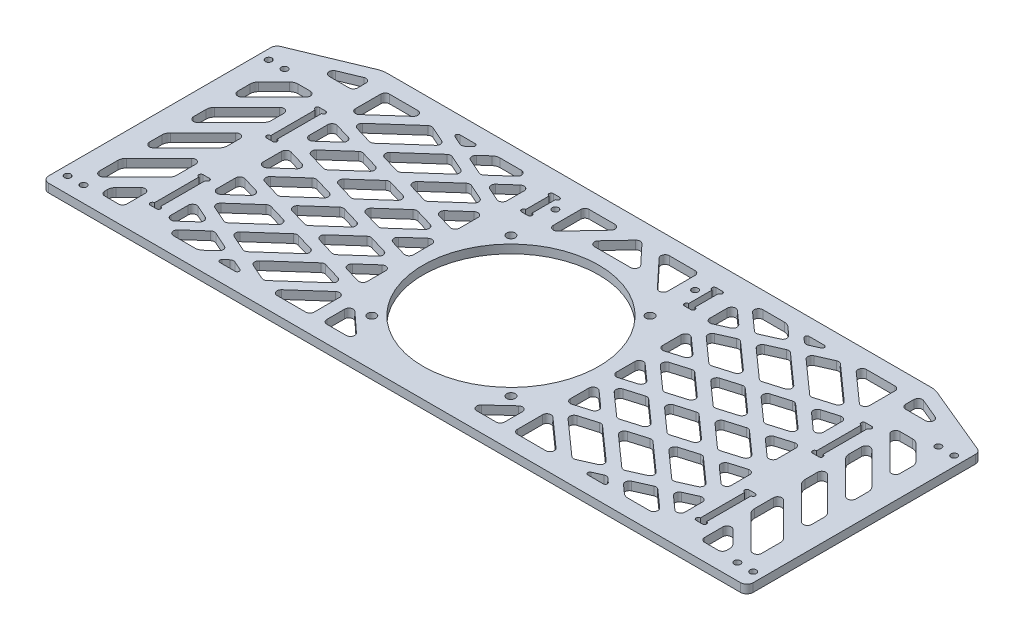
SolidWorks part; units mm, degrees
material "Thornel Mat VMA"
ref_plane "前视基准面" through (0, 0, 0) normal (0, 0, 1) x (1, 0, 0)
ref_plane "上视基准面" through (0, 0, 0) normal (0, 1, 0) x (1, 0, 0)
ref_plane "右视基准面" through (0, 0, 0) normal (1, 0, 0) x (0, 0, -1)
sketch "草图1" plane through (0, 0, 0) normal (0, 1, 0) x (1, 0, 0)
  line L6 (0, -55) -> (0, 55) construction
  line L7 (-33, 54) -> (33, 54) construction
  line L19 (-166.5, -55) -> (166.5, -55)
  line L20 (-166.5, 55) -> (-166.5, -55)
  line L21 (166.5, 55) -> (166.5, -55)
  line L24 (-130.5, 40) -> (-127.5, 40)
  line L25 (-130.5, 40) -> (-130.5, 15)
  line L26 (-130.5, 15) -> (-127.5, 15)
  line L27 (-127.5, 40) -> (-127.5, 15)
  line L30 (130.5, -40) -> (127.5, -40)
  line L31 (130.5, -15) -> (130.5, -40)
  line L32 (127.5, -15) -> (130.5, -15)
  line L33 (127.5, -40) -> (127.5, -15)
  line L34 (127.5, 40) -> (127.5, 15)
  line L35 (-127.5, -40) -> (-127.5, -15)
  line L36 (-127.5, -15) -> (-130.5, -15)
  line L37 (-130.5, -15) -> (-130.5, -40)
  line L38 (-130.5, -40) -> (-127.5, -40)
  line L39 (130.5, 15) -> (127.5, 15)
  line L40 (130.5, 40) -> (130.5, 15)
  line L41 (130.5, 40) -> (127.5, 40)
  line L47 (-154.5, -47.5) -> (-162, -47.5) construction
  line L48 (-154.5, -47.5) -> (-154.5, 47.5) construction
  line L49 (-154.5, 47.5) -> (-162, 47.5) construction
  line L50 (-162, -47.5) -> (-162, 47.5) construction
  line L51 (-166.5, 55) -> (-130.5, 70)
  line L52 (-130.5, 70) -> (130.5, 70)
  line L56 (166.5, 55) -> (130.5, 70)
  line L57 (-166.5, 0) -> (0, 0) construction
  line L58 (-130.5, 15) -> (-130.5, -15) construction
  circle A0 centre (0, 0) radius 41.5
  circle A3 centre (-33, 54) radius 1.5
  circle A5 centre (33, 54) radius 1.5
  circle A8 centre (-162, 47.5) radius 1.5
  circle A9 centre (-154.5, 47.5) radius 1.5
  circle A10 centre (-154.5, -47.5) radius 1.5
  circle A11 centre (-162, -47.5) radius 1.5
  circle A12 centre (154.5, -47.5) radius 1.5
  circle A13 centre (162, -47.5) radius 1.5
  circle A14 centre (154.5, 47.5) radius 1.5
  circle A15 centre (162, 47.5) radius 1.5
  point P11 (0, 54)
  point P13 (-130.5, 0)
  point P16 (-154.5, 0)
  dimension "D1" = 83
  dimension "D5" = 261
  dimension "D8" = 3
  dimension "D26" = 3
  dimension "D3" = 66
  dimension "D4" = 15
  dimension "D6" = 16
  dimension "D12" = 333
  dimension "D17" = 3
  dimension "D18" = 25
  dimension "D19" = 30
  dimension "D20" = 127.5
  dimension "D22" = 4.5
  dimension "D23" = 7.5
  dimension "D24" = 95
  dimension "D25" = 7.5
extrude "凸台-拉伸1" add sketch "草图1" along normal blind 4
sketch "草图2" plane through (0, 4, 0) normal (0, 1, 0) x (1, 0, 0)
  line L1 (40, 45) -> (40, 60)
  line L2 (0, 21.0132) -> (0, 0) construction
  line L3 (0, 0) -> (21.2014, 0) construction
  line L4 (-32.8805, 32.8805) -> (0, 0) construction
  line L5 (-37, 45) -> (-40, 45)
  line L6 (-37, 45) -> (-37, 60)
  line L7 (-37, 60) -> (-40, 60)
  line L8 (-40, 45) -> (-40, 60)
  line L9 (37, 60) -> (40, 60)
  line L10 (37, 45) -> (37, 60)
  line L11 (37, 45) -> (40, 45)
  line L12 (130.5, 70) -> (-130.5, 70) construction
  circle A7 centre (-32.8805, 32.8805) radius 2
  circle A9 centre (32.8805, 32.8805) radius 2
  circle A18 centre (0, 0) radius 46.5 construction
  circle A21 centre (32.8805, -32.8805) radius 2
  circle A23 centre (-32.8805, -32.8805) radius 2
  dimension "D1" = 93
  dimension "D2" = 4
  dimension "D3" = 74
  dimension "D4" = 3
  dimension "D5" = 10
  dimension "D6" = 15
  dimension "D7" = 45
extrude "切除-拉伸1" cut sketch "草图2" against normal through all
sketch "草图3" plane through (0, 4, 0) normal (0, 1, 0) x (1, 0, 0)
  line L0 (-40, 60) -> (-40, 45) construction
  line L1 (-37, 45) -> (-37, 60) construction
  line L2 (0, -55) -> (0, 55) construction
  line L5 (-130.5, 40) -> (-130.5, 15) construction
  line L6 (-127.5, 15) -> (-127.5, 40) construction
  line L7 (-130.5, -15) -> (-130.5, -40) construction
  line L8 (-127.5, -40) -> (-127.5, -15) construction
  circle A0 centre (-40, 59) radius 1
  circle A1 centre (-37, 59) radius 1
  circle A2 centre (-37, 46) radius 1
  circle A3 centre (-40, 46) radius 1
  circle A4 centre (40, 46) radius 1
  circle A5 centre (37, 46) radius 1
  circle A6 centre (37, 59) radius 1
  circle A7 centre (40, 59) radius 1
  circle A12 centre (-130.5, 39) radius 1
  circle A13 centre (-127.5, 39) radius 1
  circle A14 centre (-127.5, 16) radius 1
  circle A15 centre (-130.5, 16) radius 1
  circle A16 centre (-130.5, -16) radius 1
  circle A17 centre (-127.5, -16) radius 1
  circle A18 centre (-127.5, -39) radius 1
  circle A19 centre (-130.5, -39) radius 1
  circle A20 centre (130.5, -39) radius 1
  circle A21 centre (127.5, -39) radius 1
  circle A22 centre (127.5, -16) radius 1
  circle A23 centre (130.5, -16) radius 1
  circle A24 centre (130.5, 16) radius 1
  circle A25 centre (127.5, 16) radius 1
  circle A26 centre (127.5, 39) radius 1
  circle A27 centre (130.5, 39) radius 1
  dimension "D1" = 2
extrude "切除-拉伸2" cut sketch "草图3" against normal through all
sketch "草图12" plane through (0, 4, 0) normal (0, 1, 0) x (1, 0, 0)
  line L0 (-136.5, -7.6406) -> (-136.5, -23.0777)
  line L3 (-136.5, 13.2041) -> (-136.5, 0.8447)
  line L4 (-156.5, 14.0487) -> (-156.5, 1.6893)
  line L5 (-156.5, -6.7959) -> (-156.5, -19.1553)
  line L6 (-156.5, -27.6406) -> (-156.5, -40)
  line L9 (-136.5, -31.5629) -> (-147, -42.0629)
  line L10 (-147, -47) -> (-136.5, -47)
  line L32 (-136.5, -47) -> (-136.5, -31.5629)
  line L41 (-146.8594, 44.534) -> (-156.5, 34.8934)
  line L44 (-166.5, -55) -> (166.5, -55) construction
  line L73 (-147, -42.0629) -> (-147, -47)
  line L74 (-129.5, 63.9167) -> (-150.9, 55)
  line L75 (-150.9, 55) -> (-129.5, 55)
  line L76 (-129.5, 55) -> (-129.5, 63.9167)
  line L77 (-42, -32) -> (-25.7448, -47)
  line L78 (-25.7448, -47) -> (-42, -47)
  line L79 (-42, -47) -> (-42, -32)
  line L84 (-130.5, 70) -> (-166.5, 55) construction
  line L85 (-166.5, -55) -> (166.5, -55) construction
  line L96 (-121.5, 62) -> (-48, 62)
  line L97 (-121.5, 62) -> (-121.5, -47)
  line L99 (-121.5, -47) -> (-48, -47)
  line L102 (-48, 62) -> (-48, -47)
  line L107 (-136.5, 21.6893) -> (-156.5, 1.6893)
  line L108 (-146.8594, 44.534) -> (-134.5, 44.534)
  line L109 (-156.5, 34.8934) -> (-156.5, 22.534)
  line L110 (-156.5, -40) -> (-153.4223, -40)
  line L111 (-136.5, 34.0487) -> (-136.5, 21.6893)
  line L112 (-136.5, 13.2041) -> (-156.5, -6.7959)
  line L113 (-136.5, 0.8447) -> (-156.5, -19.1553)
  line L114 (-156.5, -27.6406) -> (-136.5, -7.6406)
  line L115 (-136.5, -23.0777) -> (-153.4223, -40)
  line L117 (-130.5, 38) -> (-130.5, 17) construction
  line L118 (-136.5, 34.0487) -> (-156.5, 14.0487)
  line L119 (-127.5, -38) -> (-127.5, -17) construction
  line L120 (-134.5, 44.534) -> (-156.5, 22.534)
  line L121 (-166.5, 55) -> (-166.5, -55) construction
  line L126 (-40, 58) -> (-40, 47) construction
  line L187 (130.5, 70) -> (-130.5, 70) construction
  line L188 (0, -2.2) -> (0, 2.2) construction
  line L189 (134.5, 44.534) -> (156.5, 22.534)
  line L190 (136.5, 34.0487) -> (156.5, 14.0487)
  line L191 (136.5, -23.0777) -> (153.4223, -40)
  line L192 (156.5, -27.6406) -> (136.5, -7.6406)
  line L193 (136.5, 0.8447) -> (156.5, -19.1553)
  line L194 (136.5, 13.2041) -> (156.5, -6.7959)
  line L195 (136.5, 34.0487) -> (136.5, 21.6893)
  line L196 (156.5, -40) -> (153.4223, -40)
  line L197 (156.5, 34.8934) -> (156.5, 22.534)
  line L198 (146.8594, 44.534) -> (134.5, 44.534)
  line L199 (136.5, 21.6893) -> (156.5, 1.6893)
  line L200 (48, 62) -> (48, -47)
  line L201 (121.5, -47) -> (48, -47)
  line L202 (121.5, 62) -> (121.5, -47)
  line L203 (121.5, 62) -> (48, 62)
  line L204 (42, -47) -> (42, -32)
  line L205 (25.7448, -47) -> (42, -47)
  line L206 (42, -32) -> (25.7448, -47)
  line L207 (129.5, 55) -> (129.5, 63.9167)
  line L208 (150.9, 55) -> (129.5, 55)
  line L209 (129.5, 63.9167) -> (150.9, 55)
  line L210 (147, -42.0629) -> (147, -47)
  line L211 (146.8594, 44.534) -> (156.5, 34.8934)
  line L212 (136.5, -47) -> (136.5, -31.5629)
  line L213 (147, -47) -> (136.5, -47)
  line L214 (136.5, -31.5629) -> (147, -42.0629)
  line L215 (156.5, -27.6406) -> (156.5, -40)
  line L216 (156.5, -6.7959) -> (156.5, -19.1553)
  line L217 (156.5, 14.0487) -> (156.5, 1.6893)
  line L218 (136.5, 13.2041) -> (136.5, 0.8447)
  line L219 (136.5, -7.6406) -> (136.5, -23.0777)
  line L220 (-27, 62) -> (-27, 42)
  line L221 (-27, 42) -> (-8.2288, 62)
  line L222 (-8.2288, 62) -> (-27, 62)
  line L223 (0, 62) -> (-13.1399, 48)
  line L224 (-13.1399, 48) -> (13.1399, 48)
  line L226 (0, 62) -> (13.1399, 48)
  line L227 (8.2288, 62) -> (27, 62)
  line L228 (27, 42) -> (8.2288, 62)
  line L229 (27, 62) -> (27, 42)
  line L230 (0, 62) -> (0, 48) construction
  circle A0 centre (-154.5, 47.5) radius 1.5 construction
  circle A1 centre (-154.5, -47.5) radius 1.5 construction
  circle A2 centre (0, 0) radius 41.5 construction
  circle A3 centre (-33, 54) radius 1.5 construction
  dimension "D3" = 8
  dimension "D17" = 15
  dimension "D27" = 6
  dimension "D11" = 7.5
  dimension "D18" = 7.5
  dimension "D24" = 6
  dimension "D4" = 6
  dimension "D5" = 6
  dimension "D6" = 6
  dimension "D7" = 6
  dimension "D8" = 135
  dimension "D9" = 7.5
  dimension "D10" = 4
  dimension "D12" = 6
  dimension "D13" = 8
  dimension "D14" = 6
  dimension "D15" = 52
  dimension "D16" = 8
  dimension "D19" = 6
  dimension "D20" = 6
  dimension "D21" = 10
  dimension "D22" = 15
  dimension "D23" = 8
  dimension "D25" = 8
  dimension "D26" = 48
  dimension "D28" = 20
extrude "切除-拉伸8" cut sketch "草图12" against normal through all
sketch "草图13" plane through (0, 4, 0) normal (0, 1, 0) x (1, 0, 0)
  line L0 (-97, 62) -> (-121.5, 40.2) construction
  line L1 (-48, 62) -> (-121.5, 62) construction
  line L2 (-121.5, 62) -> (-121.5, -47) construction
  line L3 (-72.5, 62) -> (-121.5, 18.4)
  line L4 (-121.5, 62) -> (-97, 62) construction
  line L5 (-48, 62) -> (-121.5, -3.4)
  line L6 (-121.5, -47) -> (-48, 18.4)
  line L7 (-48, -47) -> (-48, 62) construction
  line L8 (-121.5, 40.2) -> (-48, 18.4)
  line L9 (-97, -47) -> (-48, -3.4)
  line L10 (-97, 62) -> (-72.5, 62) construction
  line L11 (-121.5, -47) -> (-48, -47) construction
  line L12 (-72.5, 62) -> (-48, 62) construction
  line L13 (-121.5, -25.2) -> (-48, 40.2)
  line L14 (-121.5, 62) -> (-121.5, 40.2) construction
  line L15 (-121.5, 40.2) -> (-121.5, 18.4) construction
  line L16 (-121.5, 18.4) -> (-121.5, -3.4) construction
  line L17 (-72.5, 62) -> (-70.2588, 63.9942)
  line L18 (-121.5, 18.4) -> (-48, -3.4)
  line L19 (-121.5, -3.4) -> (-48, -25.2)
  line L20 (-121.5, -3.4) -> (-121.5, -25.2) construction
  line L21 (-121.5, -25.2) -> (-121.5, -47) construction
  line L22 (-97, 62) -> (-48, 40.2)
  line L23 (-121.5, -25.2) -> (-72.5, -47)
  line L24 (0, -2.2) -> (0, 2.2) construction
  line L25 (-97, -47) -> (-99.2412, -48.9942)
  line L26 (-72.5, -47) -> (-48, -25.2) construction
  line L27 (72.5, -47) -> (48, -25.2) construction
  line L28 (97, -47) -> (99.2412, -48.9942)
  line L29 (72.5, 62) -> (70.2588, 63.9942)
  line L33 (121.5, -25.2) -> (72.5, -47)
  line L34 (97, 62) -> (48, 40.2)
  line L35 (121.5, -3.4) -> (48, -25.2)
  line L36 (121.5, 18.4) -> (48, -3.4)
  line L38 (121.5, -25.2) -> (48, 40.2)
  line L39 (97, -47) -> (48, -3.4)
  line L40 (121.5, 40.2) -> (48, 18.4)
  line L41 (121.5, -47) -> (48, 18.4)
  line L42 (48, 62) -> (121.5, -3.4)
  line L43 (72.5, 62) -> (121.5, 18.4)
  line L44 (97, 62) -> (121.5, 40.2) construction
  dimension "D1" = 3
extrude "拉伸-薄壁1" add sketch "草图13" against normal up to surface (4 mm away) thin contours L43 L36 L39 | L3 L18 L9 | L41 L40 L44 L34 L38 L33 L35 L42 | L6 L8 L0 L22 L13 L23 L19 L5 up to face at (-146.5, 0, -17.869) thin type mid plane wall 5
sketch "草图14" plane through (0, 4, 0) normal (0, 1, 0) x (1, 0, 0)
  line L0 (97, 62) -> (121.5, 40.2) construction
  line L1 (72.5, -47) -> (48, -25.2) construction
  line L2 (-72.5, -47) -> (-48, -25.2) construction
  line L3 (-97, 62) -> (-121.5, 40.2) construction
  line L4 (97, 62) -> (121.5, 40.2)
  line L5 (72.5, -47) -> (48, -25.2)
  line L6 (-72.5, -47) -> (-48, -25.2)
  line L7 (-97, 62) -> (-121.5, 40.2)
extrude "拉伸-薄壁2" add sketch "草图14" against normal up to surface (4 mm away) thin up to face at (104.15, 0, 42.4621) thin type mid plane wall 5
fillet "圆角1" radius 3 4 edges at (-166.5, 2, -55) (166.5, 2, 55) (-166.5, 2, 55) (166.5, 2, -55)
fillet "圆角2" radius 10 2 edges at (-130.5, 2, -70) (130.5, 2, -70)
fillet "圆角3" radius 4 22 edges at (-156.5, 2, -34.8934) (-136.5, 2, -0.8447) (-156.5, 2, 6.7959) (-156.5, 2, -14.0487) (-136.5, 2, -21.6893) (-156.5, 2, 27.6406) (-136.5, 2, 23.0777) (-146.8594, 2, -44.534) (147, 2, 42.0629) (156.5, 2, 27.6406) (156.5, 2, 6.7959) (136.5, 2, 23.0777) (136.5, 2, -0.8447) (136.5, 2, -21.6893) (156.5, 2, -14.0487) (156.5, 2, -34.8934) (146.8594, 2, -44.534) (-68.7391, 2, -62) (68.7391, 2, -62) (100.7609, 2, 47) (-100.7609, 2, 47) (-147, 2, 42.0629)
fillet "圆角4" radius 1 8 edges at (76.2609, 2, -62) (90.8497, 2, -62) (-76.2609, 2, -62) (-90.8497, 2, -62) (93.2391, 2, 47) (78.6503, 2, 47) (-78.6503, 2, 47) (-93.2391, 2, 47)
fillet "圆角5" radius 2 217 edges at (156.5, 2, 40) (-156.5, 2, 40) (-81.1238, 2, -57.673) (-109.724, 2, 33.1754) (-121.5, 2, 43.6536) (-121.5, 2, 27.9363) (-48, 2, -21.0076) (-61.3564, 2, -24.9691) (-48, 2, -36.8536) (-117.7391, 2, 47) (-104.7095, 2, 35.4063) (-93.3907, 2, 40.442) (-88.3762, 2, 42.673) (-121.5, 2, 6.0076) (-108.1436, 2, 9.9691) (-121.5, 2, 21.8536) (-121.5, 2, -37.5924) (-108.1436, 2, -33.6309) (-121.5, 2, -21.7464) (-121.5, 2, -15.7924) (-108.1436, 2, -11.8309) (-121.5, 2, 0.0536) (-64.7905, 2, -50.4063) (-76.1093, 2, -55.442) (-51.7609, 2, -62) (-59.776, 2, -48.1754) (-48, 2, -58.6536) (-48, 2, -42.9363) (-48, 2, 0.7924) (-61.3564, 2, -3.1691) (-48, 2, -15.0536) (-61.3564, 2, 18.6309) (-48, 2, 6.7464) (-48, 2, 22.5924) (-100.6093, 2, 31.758) (-84.1273, 2, 17.0923) (-71.3936, 2, 20.8691) (-89.2905, 2, 36.7937) (-116.9427, 2, 24.4913) (-102.5023, 2, 11.6423) (-89.7686, 2, 15.4191) (-105.6238, 2, 29.527) (-84.1273, 2, -4.7077) (-71.3936, 2, -0.9309) (-85.3727, 2, 11.5077) (-98.1064, 2, 7.7309) (-65.7523, 2, -21.0577) (-53.0186, 2, -17.2809) (-66.9977, 2, -4.8423) (-79.7314, 2, -8.6191) (-85.3727, 2, -32.0923) (-98.1064, 2, -35.8691) (-80.2095, 2, -51.7937) (-68.8907, 2, -46.758) (-116.4814, 2, 2.2809) (-102.5023, 2, -10.1577) (-89.7686, 2, -6.3809) (-103.7477, 2, 6.0577) (-98.1064, 2, -14.0691) (-84.1273, 2, -26.5077) (-71.3936, 2, -22.7309) (-85.3727, 2, -10.2923) (-52.5573, 2, -39.4913) (-66.9977, 2, -26.6423) (-79.7314, 2, -30.4191) (-63.8762, 2, -44.527) (-89.7686, 2, -28.1809) (-103.7477, 2, -15.7423) (-116.4814, 2, -19.5191) (-102.5023, 2, -31.9577) (-53.0186, 2, 4.5191) (-66.9977, 2, 16.9577) (-79.7314, 2, 13.1809) (-65.7523, 2, 0.7423) (-156.5, 2, -1.6893) (-136.5, 2, -34.0487) (0, 2, -62) (13.1399, 2, -48) (-13.1399, 2, -48) (-156.5, 2, 19.1553) (-136.5, 2, -13.2041) (-136.5, 2, 7.6406) (-153.4223, 2, 40) (147, 2, 47) (136.5, 2, 47) (136.5, 2, 31.5629) (129.5, 2, -63.9167) (150.9, 2, -55) (129.5, 2, -55) (42, 2, 32) (42, 2, 47) (25.7448, 2, 47) (156.5, 2, -1.6893) (136.5, 2, -34.0487) (156.5, 2, -22.534) (134.5, 2, -44.534) (156.5, 2, 19.1553) (136.5, 2, -13.2041) (153.4223, 2, 40) (136.5, 2, 7.6406) (-150.9, 2, -55) (-129.5, 2, -63.9167) (-129.5, 2, -55) (-25.7448, 2, 47) (-42, 2, 47) (-42, 2, 32) (-27, 2, -42) (-27, 2, -62) (-8.2288, 2, -62) (-156.5, 2, -22.534) (-134.5, 2, -44.534) (27, 2, -62) (27, 2, -42) (8.2288, 2, -62) (-136.5, 2, 31.5629) (-136.5, 2, 47) (-147, 2, 47) (116.4814, 2, 2.2809) (103.7477, 2, 6.0577) (89.7686, 2, -6.3809) (102.5023, 2, -10.1577) (53.0186, 2, -17.2809) (65.7523, 2, -21.0577) (79.7314, 2, -8.6191) (66.9977, 2, -4.8423) (98.1064, 2, -14.0691) (85.3727, 2, -10.2923) (71.3936, 2, -22.7309) (84.1273, 2, -26.5077) (116.4814, 2, -19.5191) (103.7477, 2, -15.7423) (89.7686, 2, -28.1809) (102.5023, 2, -31.9577) (102.5023, 2, 11.6423) (116.9427, 2, 24.4913) (105.6238, 2, 29.527) (89.7686, 2, 15.4191) (84.1273, 2, -4.7077) (98.1064, 2, 7.7309) (85.3727, 2, 11.5077) (71.3936, 2, -0.9309) (100.6093, 2, 31.758) (89.2905, 2, 36.7937) (71.3936, 2, 20.8691) (84.1273, 2, 17.0923) (79.7314, 2, 13.1809) (66.9977, 2, 16.9577) (53.0186, 2, 4.5191) (65.7523, 2, 0.7423) (66.9977, 2, -26.6423) (52.5573, 2, -39.4913) (63.8762, 2, -44.527) (79.7314, 2, -30.4191) (85.3727, 2, -32.0923) (68.8907, 2, -46.758) (80.2095, 2, -51.7937) (98.1064, 2, -35.8691) (59.776, 2, -48.1754) (48, 2, -42.9363) (48, 2, -58.6536) (81.1238, 2, -57.673) (76.1093, 2, -55.442) (64.7905, 2, -50.4063) (51.7609, 2, -62) (48, 2, -15.0536) (61.3564, 2, -3.1691) (48, 2, 0.7924) (108.1436, 2, 9.9691) (121.5, 2, 6.0076) (121.5, 2, 21.8536) (88.3762, 2, 42.673) (48, 2, 6.7464) (61.3564, 2, 18.6309) (48, 2, 22.5924) (108.1436, 2, -11.8309) (121.5, 2, -15.7924) (121.5, 2, 0.0536) (48, 2, -36.8536) (61.3564, 2, -24.9691) (48, 2, -21.0076) (121.5, 2, -21.7464) (108.1436, 2, -33.6309) (121.5, 2, -37.5924) (109.724, 2, 33.1754) (121.5, 2, 27.9363) (121.5, 2, 43.6536) (93.3907, 2, 40.442) (104.7095, 2, 35.4063) (117.7391, 2, 47) (116.4814, 2, -41.3191) (103.7477, 2, -37.5423) (85.224, 2, -54.0246) (96.5429, 2, -59.0604) (121.5, 2, -62) (121.5, 2, -43.5464) (100.7609, 2, -62) (53.0186, 2, 26.3191) (65.7523, 2, 22.5423) (84.276, 2, 39.0246) (72.9571, 2, 44.0604) (48, 2, 47) (48, 2, 28.5464) (68.7391, 2, 47) (-84.276, 2, 39.0246) (-65.7523, 2, 22.5423) (-53.0186, 2, 26.3191) (-72.9571, 2, 44.0604) (-48, 2, 47) (-68.7391, 2, 47) (-48, 2, 28.5464) (-85.224, 2, -54.0246) (-103.7477, 2, -37.5423) (-116.4814, 2, -41.3191) (-96.5429, 2, -59.0604) (-121.5, 2, -62) (-100.7609, 2, -62) (-121.5, 2, -43.5464)
